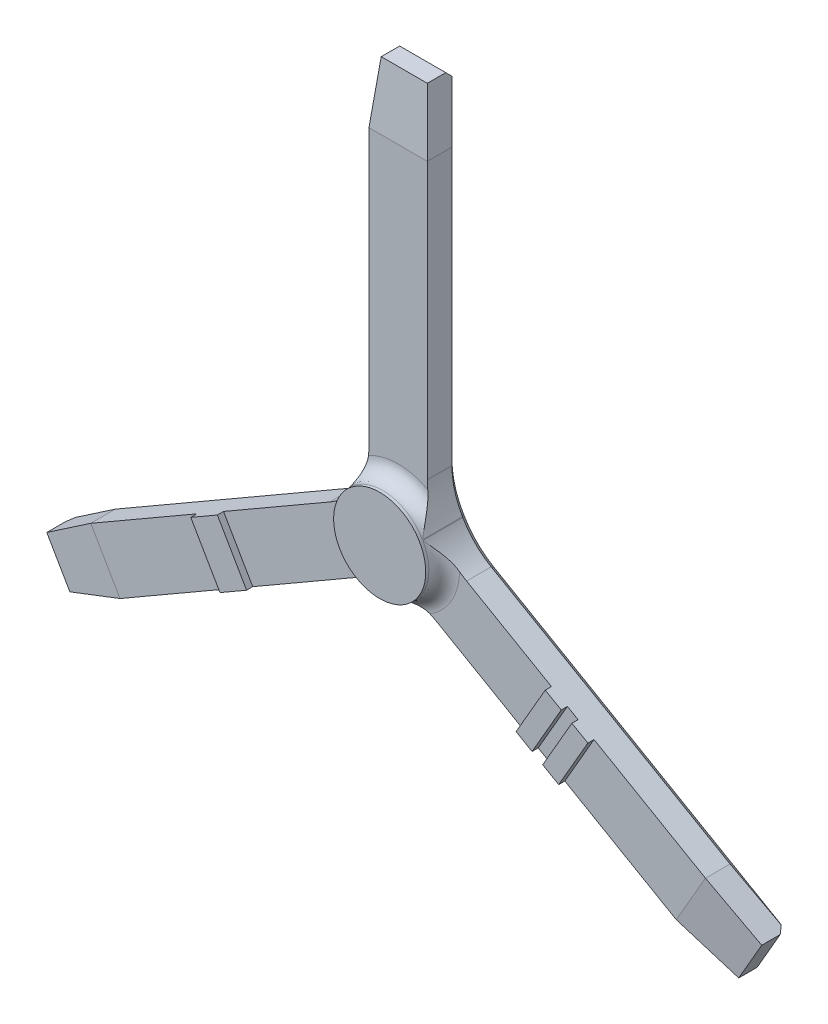
SolidWorks part; units mm, degrees
ref_plane "Front Plane" through (0, 0, 0) normal (0, 0, 1) x (1, 0, 0)
ref_plane "Top Plane" through (0, 0, 0) normal (0, 1, 0) x (1, 0, 0)
ref_plane "Right Plane" through (0, 0, 0) normal (1, 0, 0) x (0, 0, -1)
sketch "Sketch1" plane through (0, 0, 0) normal (0, 0, 1) x (1, 0, 0)
  line L0 (-1.9, 24) -> (1.9, 24) construction
  line L1 (0, 0) -> (0, 24) construction
  line L2 (-1.9, 24) -> (-1.9, 26)
  line L3 (-1.9, 26) -> (1.9, 26)
  line L4 (1.9, 26) -> (1.9, 24)
  line L5 (23.4667, -11.3546) -> (21.5667, -14.6454)
  line L6 (21.5667, -14.6454) -> (19.8346, -13.6454)
  line L7 (21.7346, -10.3546) -> (23.4667, -11.3546)
  line L8 (-21.5667, -14.6454) -> (-23.4667, -11.3546)
  line L9 (-23.4667, -11.3546) -> (-21.7346, -10.3546)
  line L10 (-19.8346, -13.6454) -> (-21.5667, -14.6454)
  line L11 (0, 0) -> (1.9, 24) construction
  line L12 (0, 0) -> (19.8346, -13.6454) construction
  line L13 (-1.9, 24) -> (-1.9, 1.097)
  line L14 (-1.9, 1.097) -> (-21.7346, -10.3546)
  line L15 (-19.8346, -13.6454) -> (0, -2.1939)
  line L16 (0, -2.1939) -> (19.8346, -13.6454)
  line L17 (21.7346, -10.3546) -> (1.9, 1.097)
  line L18 (1.9, 1.097) -> (1.9, 24)
  circle A0 centre (0, 0) radius 24 construction
  dimension "D1" = 48
  dimension "D2" = 3.8
  dimension "D3" = 2
  dimension "D4" = 120
  dimension "D5" = 24.0751
  dimension "D6" = 3
extrude "Boss-Extrude1" add sketch "Sketch1" along normal blind 2 contours L18 A0 L13 L14 L15 L16 L17 region at (0, 0, 0)
chamfer "Chamfer1" distance 4 distance2 0.4 3 edges at (22.5167, -13, 2) (-22.5167, -13, 2) (0, 26, 2) first distance on face at (0, 0, 2)
chamfer "Chamfer2" distance 0.4 distance2 4 3 edges at (23.4667, -11.3546, 0.8) (-1.9, 26, 0.8) (-21.5667, -14.6454, 0.8) first distance on face at (22.5167, -13, 0.8) first distance on face at (0, 26, 0.8) first distance on face at (-22.5167, -13, 0.8)
chamfer "Chamfer3" distance 4 distance2 0.4 3 edges at (1.9, 26, 0.8) (21.5667, -14.6454, 0.8) (-23.4667, -11.3546, 0.8) first distance on face at (1.9, 15.2388, 1.12) first distance on face at (12.2472, -9.2648, 1.12) first distance on face at (-14.1472, -5.9739, 1.12)
sketch "Sketch2" plane through (0, 0, 0) normal (0, 0, -1) x (-1, 0, 0)
  circle A0 centre (0, 0) radius 3
  dimension "D1" = 6
extrude "Boss-Extrude2" add sketch "Sketch2" against normal blind 3.2
fillet "Fillet1" radius 5 6 edges at (1.9, 2.3216, 1) (2.9606, 0.4846, 1) (1.0606, -2.8063, 1) (-1.0606, -2.8063, 1) (-2.9606, 0.4846, 1) (-1.9, 2.3216, 1)
fillet "Fillet2" radius 1 3 edges at (0, 3, 2) (2.5981, -1.5, 2) (-2.5981, -1.5, 2)
chamfer "Chamfer4" distance 0.4 angle 45 18 edges at (22.5167, -13, 0) (-22.5167, -13, 0) (0, 26, 0) (12.2293, -4.8667, 0) (3.4082, 0.4282, 0) (2.5981, 1.5, 0) (2.0749, 2.7374, 0) (1.9, 13.0242, 0) (-12.2293, -4.8667, 0) (-3.4082, 0.4282, 0) (-2.5981, 1.5, 0) (-2.0749, 2.7374, 0) (-1.9, 13.0242, 0) (10.3293, -8.1576, 0) (1.3332, -3.1657, 0) (0, -3, 0) (-1.3332, -3.1657, 0) (-10.3293, -8.1576, 0)
sketch "Sketch3" plane through (0, 0, 2) normal (0, 0, 1) x (1, 0, 0)
  line L0 (-12.2293, -4.8667) -> (-10.3293, -8.1576) construction
  line L1 (-4.4561, -0.3788) -> (-20.0026, -9.3546) construction
  line L2 (-2.5561, -3.6697) -> (-18.1026, -12.6454) construction
  line L3 (-13.0953, -5.3667) -> (-11.1953, -8.6576)
  line L4 (2.5561, -3.6697) -> (18.1026, -12.6454) construction
  line L5 (10.3293, -8.1576) -> (12.2293, -4.8667) construction
  line L6 (20.0026, -9.3546) -> (4.4561, -0.3788) construction
  line L7 (-13.0953, -5.3667) -> (-11.3633, -4.3667)
  line L8 (-11.1953, -8.6576) -> (-9.4633, -7.6576)
  line L9 (-11.3633, -4.3667) -> (-9.4633, -7.6576)
  line L10 (-13.0953, -5.3667) -> (-9.4633, -7.6576) construction
  line L11 (-11.1953, -8.6576) -> (-11.3633, -4.3667) construction
  line L12 (11.7097, -4.5667) -> (9.8097, -7.8576)
  line L13 (11.7097, -4.5667) -> (12.7489, -5.1667)
  line L14 (9.8097, -7.8576) -> (10.8489, -8.4576)
  line L15 (12.7489, -5.1667) -> (10.8489, -8.4576)
  line L16 (11.7097, -4.5667) -> (10.8489, -8.4576) construction
  line L17 (9.8097, -7.8576) -> (12.7489, -5.1667) construction
  line L18 (8.0776, -6.8576) -> (9.1169, -7.4576)
  line L19 (11.0169, -4.1667) -> (9.1169, -7.4576)
  line L20 (9.9776, -3.5667) -> (8.0776, -6.8576)
  line L21 (9.9776, -3.5667) -> (11.0169, -4.1667)
  point P13 (-11.2793, -6.5121)
  point P14 (11.2793, -6.5121)
  dimension "D1" = 2
  dimension "D2" = 1.2
extrude "Boss-Extrude3" add sketch "Sketch3" along normal blind 0.4
